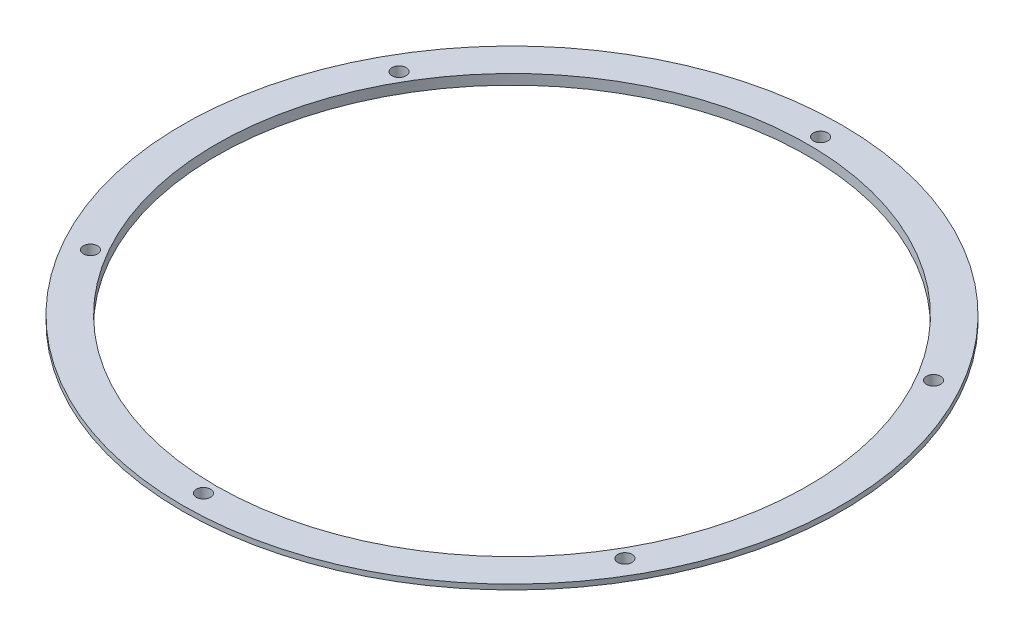
SolidWorks part; units mm, degrees
ref_plane "Front Plane" through (0, 0, 0) normal (0, 0, 1) x (1, 0, 0)
ref_plane "Top Plane" through (0, 0, 0) normal (0, 1, 0) x (1, 0, 0)
ref_plane "Right Plane" through (0, 0, 0) normal (1, 0, 0) x (0, 0, -1)
sketch "Sketch1" plane through (0, 0, 0) normal (0, 1, 0) x (1, 0, 0)
  line L0 (0, 154.5) -> (0, 0) construction
  line L1 (0, 160.85) -> (0, 148.15) construction
  line L2 (0, -55) -> (0, 55) construction
  circle A0 centre (0, 0) radius 154.5 construction
  circle A1 centre (0, 154.5) radius 3.556
  circle A2 centre (133.8009, 77.25) radius 3.556
  circle A3 centre (133.8009, -77.25) radius 3.556
  circle A4 centre (0, -154.5) radius 3.556
  circle A5 centre (-133.8009, -77.25) radius 3.556
  circle A6 centre (-133.8009, 77.25) radius 3.556
  circle A7 centre (0, 0) radius 160.85
  circle A8 centre (0, 0) radius 148.15
  point P17 (0, 0)
  point P20 (0, 154.5)
  dimension "D1" = 7.112
  dimension "D2" = 309
  dimension "D6" = 12.7
  dimension "D4" = 60
  dimension "D5" = 60
  dimension "D3" = 6
extrude "Boss-Extrude1" add sketch "Sketch1" along normal blind 5.08
sketch "Sketch2" plane through (0, 5.08, 0) normal (0, 1, 0) x (1, 0, 0)
  circle A0 centre (0, 0) radius 165
  circle A1 centre (0, 0) radius 160.85
  circle A2 centre (0, 0) radius 160.85 construction
  dimension "D1" = 330
extrude "Boss-Extrude2" add sketch "Sketch2" against normal blind 2.54
